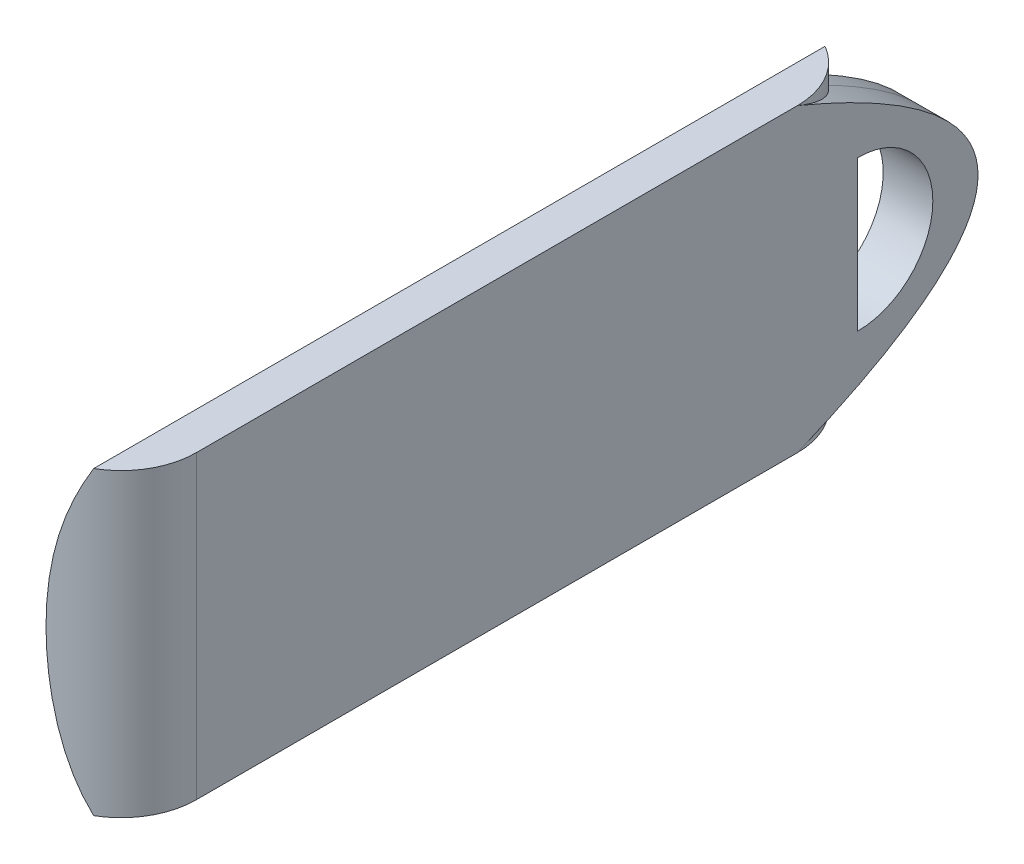
SolidWorks part; units mm, degrees
ref_plane "Plan de face" through (0, 0, 0) normal (0, 0, 1) x (1, 0, 0)
ref_plane "Plan de dessus" through (0, 0, 0) normal (0, 1, 0) x (1, 0, 0)
ref_plane "Plan de droite" through (0, 0, 0) normal (1, 0, 0) x (0, 0, -1)
sketch "Esquisse1" plane through (0, 0, 0) normal (1, 0, 0) x (0, 0, -1)
  line L1 (-25, 10) -> (25, 10)
  line L2 (-25, 10) -> (-25, -10)
  line L3 (-25, -10) -> (25, -10)
  line L4 (25, 10) -> (25, -10)
  line L5 (-25, 10) -> (25, -10) construction
  line L6 (-25, -10) -> (25, 10) construction
  point P0 (0, 0)
  dimension "D1" = 20
  dimension "D2" = 50
extrude "Boss.-Extru.1" add sketch "Esquisse1" along normal blind 2.5
sketch "Esquisse2" plane through (0, 0, 25) normal (0, 0, 1) x (1, 0, 0)
  line L0 (2.5, 0) -> (-2.5, 0)
  line L1 (2.5, 10) -> (2.5, -10) construction
  line L2 (0, -10) -> (0, 10)
  spline S0 degree 2 poles (0, -10) (-5, 0) (0, 10) knots 0 0 0 1 1 1
  line M2 (0, 10) -> (0, -10)
  dimension "D1" = 5
extrude "Boss.-Extru.2" add sketch "Esquisse2" against normal up to surface (50 mm away) contours S0 L0 M2 | S0 L0 M2 region at (-1, -3.75, 25) region at (-1, 3.75, 25) up to face at (1.25, 0, -25)
fillet "Congé1" radius 5 2 edges at (2.5, 0, -25) (2.5, 0, 25)
sketch "Esquisse3" plane through (2.5, 0, 0) normal (1, 0, 0) x (0, 0, -1)
  line L4 (-20, -10) -> (20, -10) construction
  line L6 (20, 10) -> (20, -10)
  spline S0 degree 2 poles (20, 10) (44.0104, 0) (20, -10) knots 0 0 0 1 1 1
extrude "Boss.-Extru.3" add sketch "Esquisse3" against normal blind 2
sketch "Esquisse5" plane through (0.5, 0, 0) normal (-1, 0, 0) x (0, 0, 1)
  line L0 (-24, -8.1659) -> (-24, 8.1659) construction
  line L1 (-24, -5) -> (-24, 5)
  arc A0 (-24, 5) -> (-24, -5) centre (-24, 0) ccw
extrude "Enlèv. mat.-Extru.1" cut sketch "Esquisse5" against normal blind 5
sketch "Esquisse6" plane through (0.5, 0, 0) normal (-1, 0, 0) x (0, 0, 1)
  line L2 (-24, 5) -> (-24, 8.1659)
  line L3 (-24, -8.1659) -> (-24, -5)
  line L4 (-24, 5) -> (-24, 8.1659)
  line L5 (-24, -8.1659) -> (-24, -5)
  arc A2 (-24, 5) -> (-24, -5) centre (-24, 0) ccw
  arc A4 (-24, 5) -> (-24, -5) centre (-24, 0) ccw
  parabola Q1 (-24, 8.1659) -> (-24, -8.1659) focus (-29.9228, 0) apex (-32.0052, 0)
  parabola Q2 (-24, 8.1659) -> (-24, -8.1659) focus (-29.9228, 0) apex (-32.0052, 0)
  dimension "D1" = 0
extrude "Boss.-Extru.4" add sketch "Esquisse6" along normal blind 1.3
sketch "Esquisse7" plane through (0, 0, 0) normal (1, 0, 0) x (0, 0, -1)
  text T0 "RENAULT" font "Copperplate Gothic Light" height in points 28
  point P4 (0, 0)
extrude "Boss.-Extru.5" add sketch "Esquisse7" against normal blind 3
sketch "Esquisse8" plane through (0, 0, 0) normal (1, 0, 0) x (0, 0, -1)
  text T0 "sport" font "Forte" height in points 24
extrude "Boss.-Extru.6" add sketch "Esquisse8" against normal blind 3
